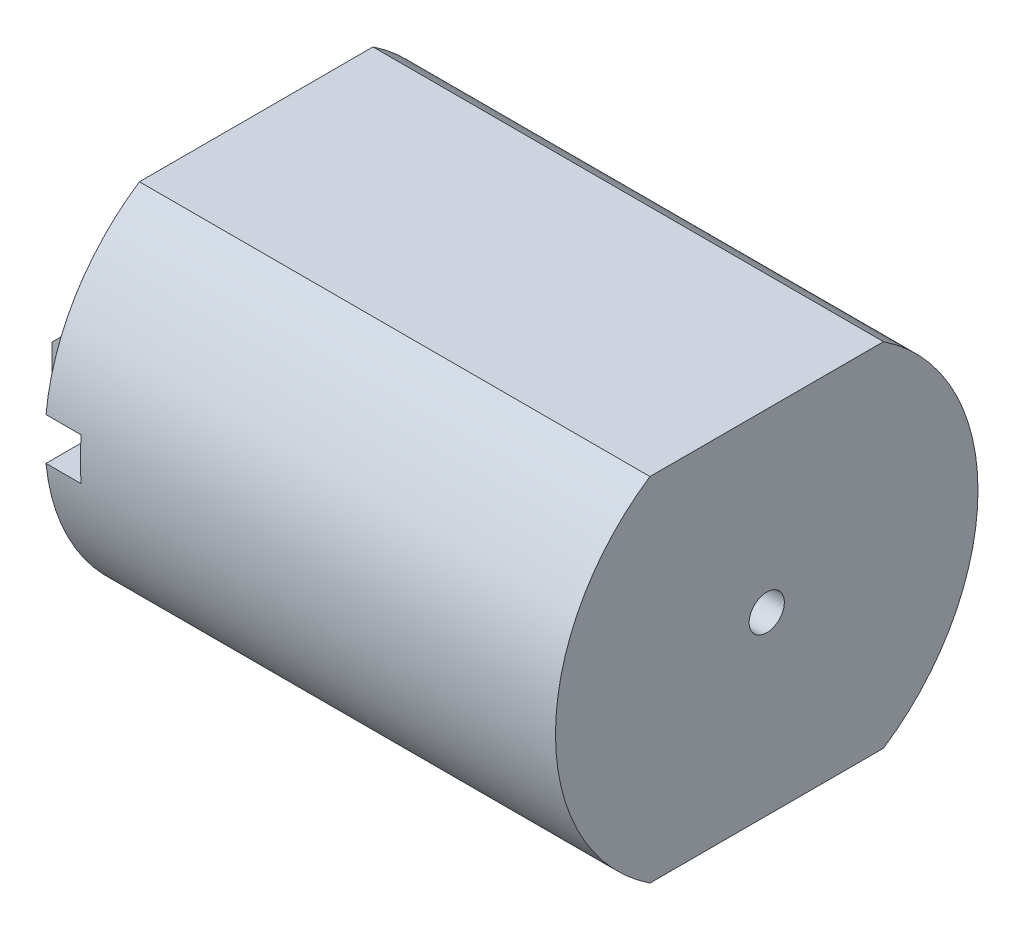
SolidWorks part; units mm, degrees
ref_plane "Alzado" through (0, 0, 0) normal (0, 0, 1) x (1, 0, 0)
ref_plane "Planta" through (0, 0, 0) normal (0, 1, 0) x (1, 0, 0)
ref_plane "Vista lateral" through (0, 0, 0) normal (1, 0, 0) x (0, 0, -1)
sketch "Croquis1" plane through (0, 0, 0) normal (1, 0, 0) x (0, 0, -1)
  line L1 (-3.3166, 5) -> (3.3166, 5)
  line L3 (-3.3166, -5) -> (3.3166, -5)
  arc A0 (-3.3166, 5) -> (-3.3166, -5) centre (0, 0) ccw
  arc A1 (3.3166, -5) -> (3.3166, 5) centre (0, 0) ccw
  dimension "D2" = 12
  dimension "D1" = 6.6332
extrude "Saliente-Extruir1" add sketch "Croquis1" along normal blind 13.5
sketch "Croquis2" plane through (0, 0, 0) normal (-1, 0, 0) x (0, 0, 1)
  line L0 (-4.9699, 0.6) -> (-4.9699, -0.6)
  line L1 (-4.9699, -0.6) -> (-5.9699, -0.6)
  line L2 (-3.3166, -5) -> (3.3166, -5)
  line L3 (3.3166, 5) -> (-3.3166, 5)
  line L4 (-3.3166, -5) -> (3.3166, -5)
  line L5 (3.3166, 5) -> (-3.3166, 5)
  line L6 (-4.9699, 0.6) -> (-5.9699, 0.6)
  line L7 (4.9699, 0.6) -> (4.9699, -0.6)
  line L8 (4.9699, -0.6) -> (5.9699, -0.6)
  line L9 (4.9699, 0.6) -> (5.9699, 0.6)
  arc A0 (-5.9699, -0.6) -> (-3.3166, -5) centre (0, 0) ccw
  arc A1 (5.9699, 0.6) -> (3.3166, 5) centre (0, 0) ccw
  arc A2 (-3.3166, 5) -> (-3.3166, -5) centre (0, 0) ccw
  arc A3 (3.3166, -5) -> (3.3166, 5) centre (0, 0) ccw
  arc A4 (-3.3166, 5) -> (-5.9699, 0.6) centre (0, 0) ccw
  arc A5 (3.3166, -5) -> (5.9699, -0.6) centre (0, 0) ccw
  point P8 (-4.9699, 0)
  point P13 (4.9699, 0)
  dimension "D2" = 1.2
  dimension "D3" = 1
  dimension "D4" = 1
  dimension "D5" = 1.2
  dimension "D1" = 0
extrude "Saliente-Extruir2" add sketch "Croquis2" along normal blind 1
sketch "Croquis3" plane through (-1, 0, 0) normal (-1, 0, 0) x (0, 0, 1)
  circle A0 centre (0, 0) radius 2.5
  circle A1 centre (0, 0) radius 0.5
  dimension "D1" = 1
  dimension "D2" = 5
extrude "Saliente-Extruir3" add sketch "Croquis3" along normal blind 1
fillet "Redondeo1" radius 0.25 1 edges at (-2, 0, 2.5)
extrude "Cortar-Extruir1" cut sketch "Croquis3<2>" against normal up to surface (14.5 mm away) contours A1 region at (-1, 0, 0) up to face at (13.5, 0, 0)
sketch "Croquis3<2>" plane through (-1, 0, 0) normal (-1, 0, 0) x (0, 0, 1) same geometry as "Croquis3"
ref_plane "Plano1" through (0, 0, 4) normal (0, 0, 1) x (1, 0, 0)
sketch "Croquis4" plane through (0, 0, 4) normal (0, 0, 1) x (1, 0, 0)
  line L1 (-2.55, 0.75) -> (-1, 0.75)
  line L2 (-2.8, 0.5) -> (-2.8, -0.5)
  line L3 (-2.55, -0.75) -> (-1, -0.75)
  line L4 (-1, 0.75) -> (-1, -0.75)
  line L5 (-2.8, 0.75) -> (-1, -0.75) construction
  line L6 (-2.8, -0.75) -> (-1, 0.75) construction
  line L7 (-1, 2.5) -> (-1, -2.5) construction
  line L8 (-2.8, 0.5) -> (-2.55, 0.75)
  line L9 (-2.8, -0.5) -> (-2.55, -0.75)
  circle A0 centre (-2.15, 0) radius 0.5
  point P0 (-1.9, 0)
  dimension "D3" = 1
  dimension "D1" = 1.5
  dimension "D2" = 1.8
  dimension "D4" = 0.25
extrude "Saliente-Extruir4" add sketch "Croquis4" against normal blind 0.25
pattern_linear "MatrizL1" count 2 spacing 8 along (0, 0, -1) of "Saliente-Extruir4"
